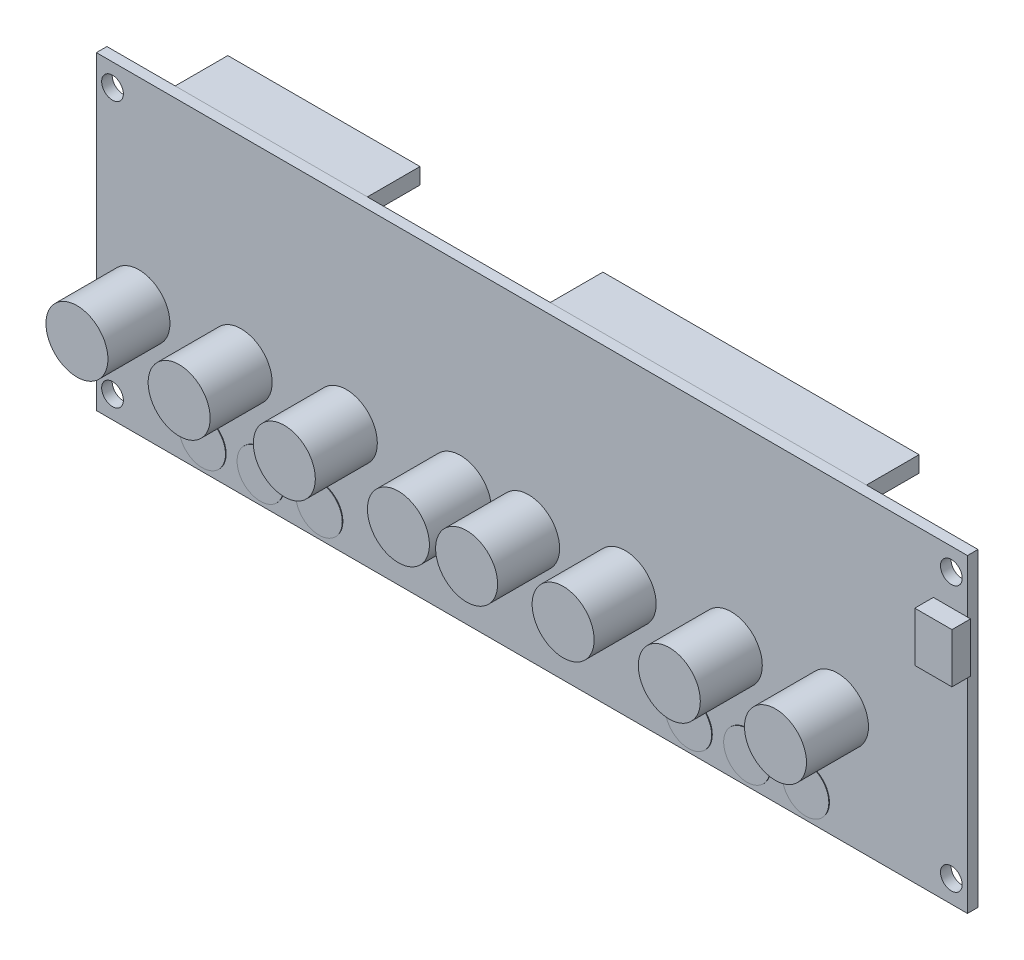
SolidWorks part; units mm, degrees
note: The reader was unsure of these and kept them because the rebuilt part matched: shared geometry of "Sketch1<3>", "Sketch1<4>", "Sketch1<5>", "Sketch1<6>", "Sketch1<7>".
ref_plane "Front Plane" through (0, 0, 0) normal (0, 0, 1) x (1, 0, 0)
ref_plane "Top Plane" through (0, 0, 0) normal (0, 1, 0) x (1, 0, 0)
ref_plane "Right Plane" through (0, 0, 0) normal (1, 0, 0) x (0, 0, -1)
sketch "Sketch1" plane through (0, 0, 0) normal (0, 0, 1) x (1, 0, 0)
  line L0 (0, 44.462) -> (0, -56.3186) construction
  line L1 (-70.25, 25) -> (70.25, 25)
  line L2 (-70.25, 25) -> (-70.25, -25)
  line L3 (-70.25, -25) -> (70.25, -25)
  line L4 (70.25, 25) -> (70.25, -25)
  line L5 (-86.948, 0) -> (103.7447, 0) construction
  line L6 (-74.4675, -6.9) -> (73.4013, -6.9) construction
  line L7 (70.75, 16.4) -> (70.75, 8.4)
  line L9 (70.25, 16.4) -> (70.25, 8.4)
  line L11 (64.75, 16.4) -> (64.75, 8.4)
  line L12 (64.75, 16.4) -> (70.75, 16.4)
  line L13 (64.75, 8.4) -> (70.75, 8.4)
  line L15 (-59.25, 24.99) -> (-28.25, 24.99)
  line L16 (-59.25, 24.99) -> (-59.25, 22.4)
  line L17 (-59.25, 22.4) -> (-28.25, 22.4)
  line L18 (-28.25, 24.99) -> (-28.25, 22.4)
  line L19 (1.25, 24.99) -> (52.25, 24.99)
  line L20 (1.25, 24.99) -> (1.25, 22.4)
  line L21 (1.25, 22.4) -> (52.25, 22.4)
  line L22 (52.25, 24.99) -> (52.25, 22.4)
  circle A0 centre (-67.65, 21.4) radius 1.75
  circle A1 centre (67.65, 21.4) radius 1.75
  circle A2 centre (-67.65, -21.4) radius 1.75
  circle A3 centre (67.65, -21.4) radius 1.75
  circle A4 centre (-46.9001, -6.9) radius 5
  circle A5 centre (-63.3868, -6.9) radius 5
  circle A6 centre (-29.9348, -6.9) radius 5
  circle A7 centre (-11.5336, -6.9) radius 5
  circle A8 centre (-0.5342, -6.9) radius 5
  circle A9 centre (15.0358, -6.9) radius 5
  circle A10 centre (32.1598, -6.9) radius 5
  circle A11 centre (49.284, -6.9) radius 5
  circle A12 centre (-53.074, -20.6) radius 3.75
  circle A13 centre (-43.7069, -20.6) radius 3.75
  circle A14 centre (-34.2423, -20.6) radius 3.75
  circle A15 centre (25.3434, -20.6) radius 3.75
  circle A16 centre (34.779, -20.6) radius 3.75
  circle A17 centre (44.2377, -20.6) radius 3.75
  dimension "D3" = 3.5
  dimension "D6" = 10
  dimension "D26" = 7.5
  dimension "D1" = 140.5
  dimension "D2" = 50
  dimension "D4" = 3.6
  dimension "D5" = 2.6
  dimension "D7" = 6.9
  dimension "D9" = 8
  dimension "D8" = 8.6
  dimension "D10" = 6
  dimension "D19" = 0.5
  dimension "D20" = 2.6
  dimension "D21" = 31
  dimension "D22" = 51
  dimension "D23" = 11
  dimension "D24" = 18
  dimension "D25" = 0.01
  dimension "D27" = 4.4
  dimension "D28" = 42.8
  dimension "D29" = 135.3
extrude "Boss-Extrude1" add sketch "Sketch1" along normal blind 1.7 contours L1 L4 L3 L2
extrude "Boss-Extrude2" add sketch "Sketch1<3>" along normal blind 10 from surface at 1.7 contours A9 | A8 | A7 | A6 | A4 | A5 | A11 | A10 starting at face at (0, 0, 1.7)
sketch "Sketch1<3>" plane through (0, 0, 0) normal (0, 0, 1) x (1, 0, 0) same geometry as "Sketch1"
extrude "Boss-Extrude3" add sketch "Sketch1<4>" along normal blind 3 from surface at 1.7 contours L7 L13 L11 L12 starting at face at (4.4658, -6.9, 1.7)
sketch "Sketch1<4>" plane through (0, 0, 0) normal (0, 0, 1) x (1, 0, 0) same geometry as "Sketch1"
extrude "Cut-Extrude1" cut sketch "Sketch1<5>" along normal through all contours A2 | A1 | A0 | A3
sketch "Sketch1<5>" plane through (0, 0, 0) normal (0, 0, 1) x (1, 0, 0) same geometry as "Sketch1"
extrude "Boss-Extrude4" add sketch "Sketch1<6>" against normal blind 8.5 contours L20 L21 L22 L19 | L16 L17 L18 L15
sketch "Sketch1<6>" plane through (0, 0, 0) normal (0, 0, 1) x (1, 0, 0) same geometry as "Sketch1"
extrude "Boss-Extrude5" add sketch "Sketch1<7>" against normal blind 0.1 and the other way offset from surface (1.8 mm away) 0.1 contours A17 | A16 | A15 | A12 | A13 | A14 other way up to face at (-65.9, 21.4, 1.7)
sketch "Sketch1<7>" plane through (0, 0, 0) normal (0, 0, 1) x (1, 0, 0) same geometry as "Sketch1"
